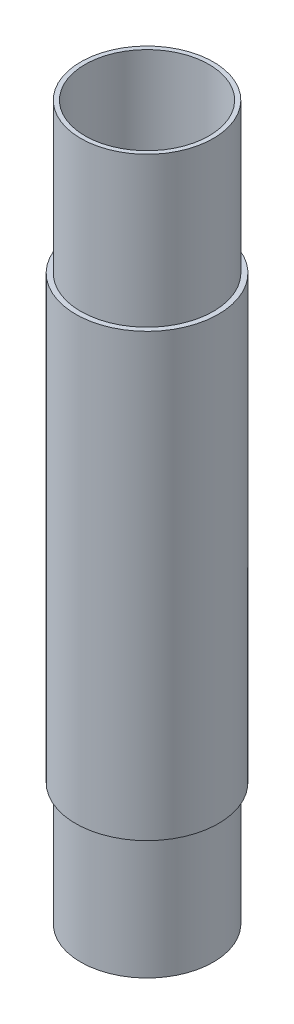
SolidWorks part; units mm, degrees
ref_plane "Front Plane" through (0, 0, 0) normal (0, 0, 1) x (1, 0, 0)
ref_plane "Top Plane" through (0, 0, 0) normal (0, 1, 0) x (1, 0, 0)
ref_plane "Right Plane" through (0, 0, 0) normal (1, 0, 0) x (0, 0, -1)
sketch "driver" plane through (0, 0, 0) normal (0, 1, 0) x (1, 0, 0)
  circle A0 centre (0, 0) radius 25.2903
  circle A1 centre (0, 0) radius 27.0675
  circle A2 centre (0, 0) radius 29.1211
  dimension "D1" = 50.5805
  dimension "D2" = 54.135
  dimension "D3" = 58.2422
extrude "Boss-Extrude1" add sketch "driver" along normal blind 80 contours A1 A0 region at (-26.3019, 0, 0)
extrude "Boss-Extrude2" add sketch "driver<3>" along normal blind 180 from offset 50 contours A2 A1 region at (-28.2974, 0, 0)
sketch "driver<3>" plane through (0, 0, 0) normal (0, 1, 0) x (1, 0, 0) same geometry as "driver"
extrude "Boss-Extrude3" add sketch "driver<4>" along normal blind 91.12 from offset 200 contours A1 A0 region at (-26.3019, 0, 0)
sketch "driver<4>" plane through (0, 0, 0) normal (0, 1, 0) x (1, 0, 0) same geometry as "driver"
